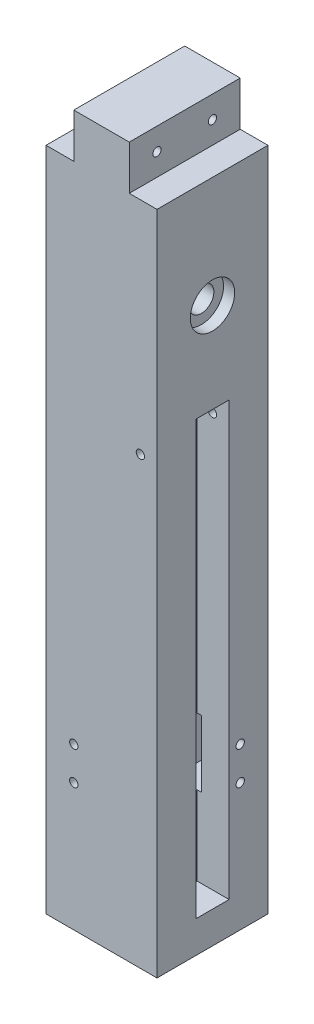
SolidWorks part; units mm, degrees
material "Pine"
ref_plane "Front Plane" through (0, 0, 0) normal (0, 0, 1) x (1, 0, 0)
ref_plane "Top Plane" through (0, 0, 0) normal (0, 1, 0) x (1, 0, 0)
ref_plane "Right Plane" through (0, 0, 0) normal (1, 0, 0) x (0, 0, -1)
sketch "Sketch1" plane through (0, 0, 0) normal (0, 0, 1) x (1, 0, 0)
  line L1 (63.5, 381) -> (-63.5, 381)
  line L2 (63.5, 381) -> (63.5, -381)
  line L3 (63.5, -381) -> (-63.5, -381)
  line L4 (-63.5, 381) -> (-63.5, -381)
  line L5 (63.5, 381) -> (-63.5, -381) construction
  line L6 (63.5, -381) -> (-63.5, 381) construction
  line L7 (31.75, 431.8) -> (-31.75, 431.8)
  line L8 (31.75, 431.8) -> (31.75, 330.2)
  line L9 (31.75, 330.2) -> (-31.75, 330.2)
  line L10 (-31.75, 431.8) -> (-31.75, 330.2)
  line L11 (31.75, 431.8) -> (-31.75, 330.2) construction
  line L12 (31.75, 330.2) -> (-31.75, 431.8) construction
  point P0 (0, 0)
  point P6 (0, 381)
  dimension "D1" = 762
  dimension "D2" = 101.6
  dimension "D3" = 63.5
  dimension "D4" = 127
extrude "Boss-Extrude1" add sketch "Sketch1" along normal blind 127 contours L10 L1 L4 L3 L2 L8 L9 | L1 L10 L9 L8 | L7 L10 L1 L8 region at (0, -12.2621, 0) region at (0, 355.6, 0) region at (0, 406.4, 0)
sketch "Sketch2" plane through (63.5, 0, 0) normal (1, 0, 0) x (0, 0, -1)
  line L0 (-63.5, -381) -> (-63.5, 49619) construction
  line L1 (-127, -381) -> (0, -381) construction
  line L2 (-127, 406.4) -> (0, 406.4) construction
  line L3 (-57.15, -482.6) -> (-69.85, -482.6)
  line L4 (-57.15, -482.6) -> (-57.15, -279.4)
  line L5 (-57.15, -279.4) -> (-69.85, -279.4)
  line L6 (-69.85, -482.6) -> (-69.85, -279.4)
  line L7 (-57.15, -482.6) -> (-69.85, -279.4) construction
  line L8 (-57.15, -279.4) -> (-69.85, -482.6) construction
  line L9 (-127, 431.8) -> (-127, 381) construction
  line L10 (0, 431.8) -> (0, 381) construction
  circle A0 centre (-63.5, 254) radius 25.4
  circle A1 centre (-63.5, 254) radius 14.2875
  circle A2 centre (-95.25, 406.4) radius 4.7625
  circle A3 centre (-31.75, 406.4) radius 4.7625
  point P4 (-63.5, -381)
  point P5 (-63.5, -381)
  dimension "D3" = 50.8
  dimension "D4" = 28.575
  dimension "D5" = 635
  dimension "D6" = 9.525
  dimension "D7" = 31.75
  dimension "D8" = 31.75
  dimension "D1" = 203.2
  dimension "D2" = 12.7
extrude "Cut-Extrude1" cut sketch "Sketch2" against normal through all contours A2 | A3 | A1 region at (63.5, 254, 63.5) region at (63.5, 406.4, 95.25) region at (63.5, 406.4, 31.75)
sketch "Sketch3" plane through (0, 0, 0) normal (0, 0, -1) x (-1, 0, 0)
  line L0 (-63.5, 381) -> (-63.5, -381) construction
  line L1 (0, -177.8) -> (-31.75, -177.8)
  line L2 (0, -177.8) -> (0, -254)
  line L3 (0, -254) -> (-31.75, -254)
  line L4 (-31.75, -177.8) -> (-31.75, -254)
  line L5 (0, -177.8) -> (-31.75, -254) construction
  line L6 (0, -254) -> (-31.75, -177.8) construction
  line L7 (-63.5, -381) -> (63.5, -381) construction
  point P0 (-15.875, -215.9)
  dimension "D1" = 76.2
  dimension "D2" = 31.75
  dimension "D3" = 31.75
  dimension "D4" = 127
extrude "Cut-Extrude2" cut sketch "Sketch3" against normal blind 63.5
extrude "Cut-Extrude3" cut sketch "Sketch2<3>" against normal blind 12.7 contours A0 A1 region at (63.5, 254, 88.1816)
sketch "Sketch2<3>" plane through (63.5, 0, 0) normal (1, 0, 0) x (0, 0, -1) same geometry as "Sketch2"
sketch "Sketch4" plane through (63.5, 0, 0) normal (1, 0, 0) x (0, 0, -1)
  line L0 (-31.75, -177.8) -> (-31.75, -254) construction
  line L4 (0, -254) -> (0, -177.8)
  line L5 (-63.5, -254) -> (0, -254)
  line L6 (-63.5, -177.8) -> (-63.5, -254)
  line L7 (0, -177.8) -> (-63.5, -177.8)
  line L8 (0, -254) -> (0, -177.8)
  line L9 (-63.5, -254) -> (0, -254)
  line L10 (-63.5, -177.8) -> (-63.5, -254)
  line L11 (0, -177.8) -> (-63.5, -177.8)
  circle A0 centre (-31.75, -234.95) radius 4.7625
  circle A1 centre (-31.75, -196.85) radius 4.7625
  point P10 (-31.75, -215.9)
  dimension "D2" = 19.05
  dimension "D3" = 19.05
  dimension "D4" = 9.525
  dimension "D5" = 31.75
  dimension "D1" = 0
extrude "Cut-Extrude4" cut sketch "Sketch4" against normal blind 69.85 contours A0 L0 | L0 A0 | A1 L0 | L0 A1 region at (63.5, -196.85, 29.7287) region at (63.5, -196.85, 33.7713) region at (63.5, -234.95, 29.7287) region at (63.5, -234.95, 33.7713)
sketch "Sketch5" plane through (-63.5, 0, 0) normal (-1, 0, 0) x (0, 0, 1)
  line L0 (127, 381) -> (127, -381) construction
  line L1 (95.25, -177.8) -> (63.5, -177.8)
  line L2 (95.25, -177.8) -> (95.25, -254)
  line L3 (95.25, -254) -> (63.5, -254)
  line L4 (63.5, -177.8) -> (63.5, -254)
  line L5 (95.25, -177.8) -> (63.5, -254) construction
  line L6 (95.25, -254) -> (63.5, -177.8) construction
  line L7 (127, -381) -> (0, -381) construction
  point P0 (79.375, -215.9)
  dimension "D1" = 76.2
  dimension "D2" = 31.75
  dimension "D3" = 31.75
  dimension "D4" = 127
extrude "Cut-Extrude6" cut sketch "Sketch5" against normal blind 63.246
sketch "Sketch6" plane through (0, 0, 127) normal (0, 0, 1) x (1, 0, 0)
  line L0 (-31.75, -177.8) -> (-31.75, -254) construction
  line L4 (-63.5, -177.8) -> (-63.5, -254)
  line L5 (-0.254, -177.8) -> (-63.5, -177.8)
  line L6 (-0.254, -254) -> (-0.254, -177.8)
  line L7 (-63.5, -254) -> (-0.254, -254)
  line L8 (-63.5, -177.8) -> (-63.5, -254)
  line L9 (-0.254, -177.8) -> (-63.5, -177.8)
  line L10 (-0.254, -254) -> (-0.254, -177.8)
  line L11 (-63.5, -254) -> (-0.254, -254)
  circle A0 centre (-31.75, -234.95) radius 4.7625
  circle A1 centre (-31.75, -196.85) radius 4.7625
  point P10 (-31.75, -215.9)
  dimension "D2" = 9.525
  dimension "D4" = 19.05
  dimension "D3" = 19.05
  dimension "D5" = 31.75
  dimension "D1" = 0
extrude "Cut-Extrude7" cut sketch "Sketch6" against normal blind 69.85 contours A0 L0 | L0 A0 | L0 A1 | A1 L0 region at (-29.7287, -196.85, 127) region at (-33.7713, -196.85, 127) region at (-29.7287, -234.95, 127) region at (-33.7713, -234.95, 127)
sketch "Sketch7" plane through (63.5, 0, 0) normal (1, 0, 0) x (0, 0, -1)
  line L4 (-82.55, 150.8125) -> (-82.55, -344.4875)
  line L5 (-44.45, 150.8125) -> (-82.55, 150.8125)
  line L6 (-44.45, -344.4875) -> (-44.45, 150.8125)
  line L7 (-82.55, -344.4875) -> (-44.45, -344.4875)
  line L8 (-82.55, 150.8125) -> (-82.55, -344.4875)
  line L9 (-44.45, 150.8125) -> (-82.55, 150.8125)
  line L10 (-44.45, -344.4875) -> (-44.45, 150.8125)
  line L11 (-82.55, -344.4875) -> (-44.45, -344.4875)
  dimension "D1" = 0
extrude "Cut-Extrude8" cut sketch "Sketch7" against normal blind 36.5125
sketch "Sketch8" plane through (0, 0, 0) normal (0, 0, -1) x (-1, 0, 0)
  line L0 (-44.45, 150.8125) -> (-44.45, -344.4875) construction
  line L8 (-31.75, -254) -> (-31.75, -177.8)
  line L9 (-26.9875, -254) -> (-31.75, -254)
  line L10 (-26.9875, -344.4875) -> (-26.9875, -254)
  line L11 (-63.5, -344.4875) -> (-26.9875, -344.4875)
  line L12 (-63.5, 150.8125) -> (-63.5, -344.4875)
  line L13 (-26.9875, 150.8125) -> (-63.5, 150.8125)
  line L14 (-26.9875, -177.8) -> (-26.9875, 150.8125)
  line L15 (-31.75, -177.8) -> (-26.9875, -177.8)
  line L16 (-31.75, -254) -> (-31.75, -177.8)
  line L17 (-26.9875, -254) -> (-31.75, -254)
  line L18 (-26.9875, -344.4875) -> (-26.9875, -254)
  line L19 (-63.5, -344.4875) -> (-26.9875, -344.4875)
  line L20 (-63.5, 150.8125) -> (-63.5, -344.4875)
  line L21 (-26.9875, 150.8125) -> (-63.5, 150.8125)
  line L22 (-26.9875, -177.8) -> (-26.9875, 150.8125)
  line L23 (-31.75, -177.8) -> (-26.9875, -177.8)
  circle A0 centre (-44.45, 128.5875) radius 4.7625
  dimension "D4" = 9.525
  dimension "D2" = 19.05
  dimension "D3" = 22.225
  dimension "D1" = 0
extrude "Cut-Extrude9" cut sketch "Sketch8" against normal through all contours A0 L0 | L0 A0 region at (42.4287, 128.5875, 0) region at (46.4713, 128.5875, 0)
